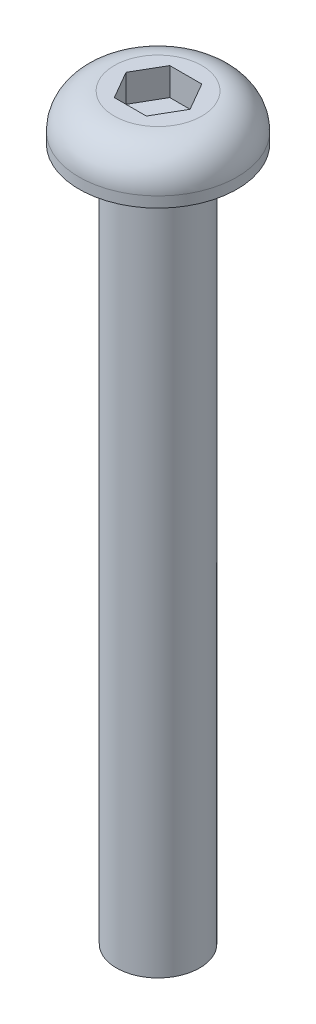
SolidWorks part; units mm, degrees
material "AISI 304"
ref_plane "Front Plane" through (0, 0, 0) normal (0, 0, 1) x (1, 0, 0)
ref_plane "Top Plane" through (0, 0, 0) normal (0, 1, 0) x (1, 0, 0)
ref_plane "Right Plane" through (0, 0, 0) normal (1, 0, 0) x (0, 0, -1)
sketch "Sketch1" plane through (0, 0, 0) normal (0, 0, 1) x (1, 0, 0)
  line L0 (1.5, 0) -> (2.85, 0)
  line L1 (2.85, 0) -> (2.85, 0.38)
  line L2 (1.58, 1.65) -> (0, 1.65)
  line L3 (1.5, 0) -> (1.5, -25)
  line L4 (1.5, -25) -> (0, -25)
  line L5 (0, -25) -> (0, 1.65)
  arc A0 (2.85, 0.38) -> (1.58, 1.65) centre (1.58, 0.38) ccw
  dimension "D1" = 1.5
  dimension "D2" = 25
  dimension "D3" = 2.85
  dimension "D4" = 1.65
  dimension "D5" = 0.38
revolve "Revolve1" add sketch "Sketch1" angle 360 about L5
sketch "Sketch2" plane through (0, 1.65, 0) normal (0, 1, 0) x (1, 0, 0)
  line L1 (0.5774, 1) -> (-0.5774, 1)
  line L2 (-0.5774, 1) -> (-1.1547, 0)
  line L3 (-1.1547, 0) -> (-0.5774, -1)
  line L4 (-0.5774, -1) -> (0.5774, -1)
  line L5 (0.5774, -1) -> (1.1547, 0)
  line L6 (1.1547, 0) -> (0.5774, 1)
  circle A0 centre (0, 0) radius 1 construction
  dimension "D1" = 2
extrude "Cut-Extrude1" cut sketch "Sketch2" against normal blind 1
